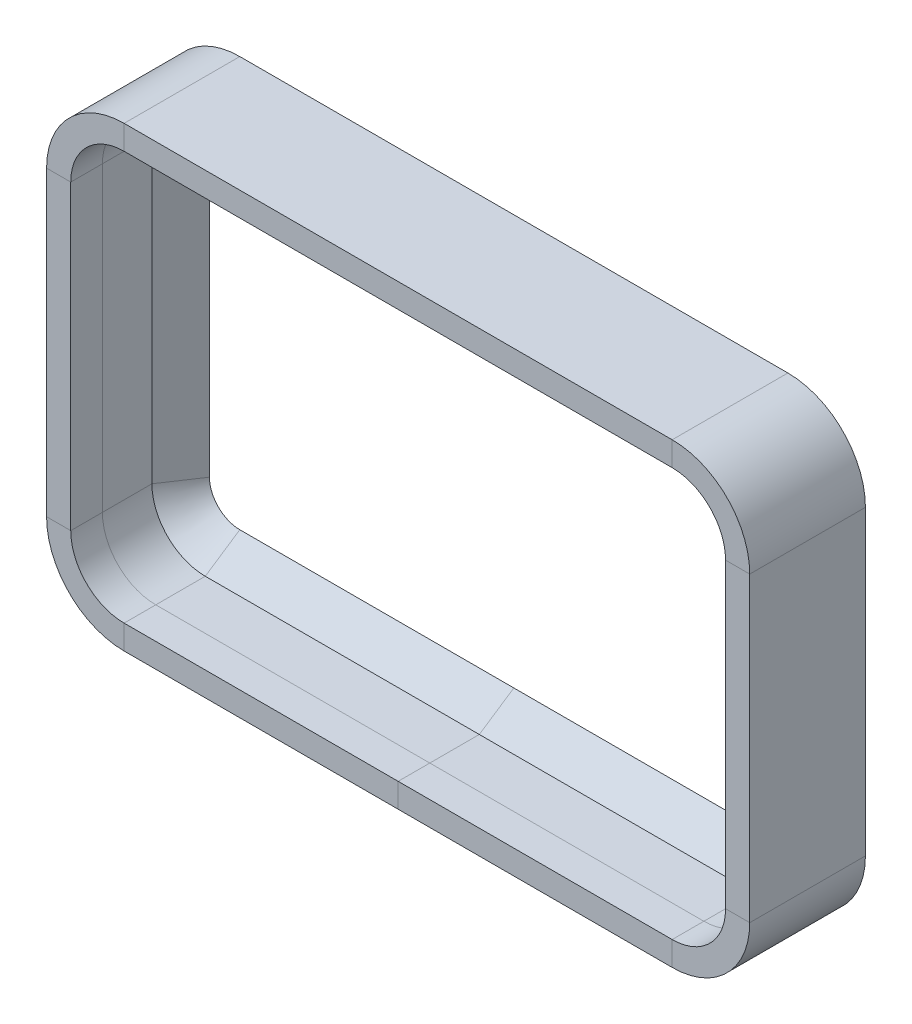
SolidWorks part; units mm, degrees
ref_plane "Plan de face" through (0, 0, 0) normal (0, 0, 1) x (1, 0, 0)
ref_plane "Plan de dessus" through (0, 0, 0) normal (0, 1, 0) x (1, 0, 0)
ref_plane "Plan de droite" through (0, 0, 0) normal (1, 0, 0) x (0, 0, -1)
sketch "Esquisse1" plane through (0, 0, 0) normal (0, 0, 1) x (1, 0, 0)
  line L1 (-39.6342, 31.8306) -> (39.6342, 31.8306)
  line L2 (-49.6342, 21.8306) -> (-49.6342, -21.8306)
  line L3 (-39.6342, -31.8306) -> (39.6342, -31.8306)
  line L4 (49.6342, 21.8306) -> (49.6342, -21.8306)
  line L5 (-49.6342, 31.8306) -> (49.6342, -31.8306) construction
  line L6 (-49.6342, -31.8306) -> (49.6342, 31.8306) construction
  arc A0 (-49.6342, -21.8306) -> (-39.6342, -31.8306) centre (-39.6342, -21.8306) ccw
  arc A1 (39.6342, -31.8306) -> (49.6342, -21.8306) centre (39.6342, -21.8306) ccw
  arc A2 (39.6342, 31.8306) -> (49.6342, 21.8306) centre (39.6342, 21.8306) cw
  arc A3 (-39.6342, 31.8306) -> (-49.6342, 21.8306) centre (-39.6342, 21.8306) ccw
  point P0 (0, 0)
  dimension "D1" = 10
sketch "Esquisse2" plane through (0, 0, 0) normal (1, 0, 0) x (0, 0, -1)
  line L0 (-2.0811, -29.5514) -> (5.0778, -29.5514)
  line L1 (5.0778, -29.5514) -> (10.0724, -26.2216)
  line L2 (10.0724, -26.2216) -> (10.0724, -33.0476)
  line L3 (10.0724, -33.0476) -> (-6.6595, -33.0476)
  line L4 (-6.6595, -33.0476) -> (-6.6595, -29.5514)
  line L5 (-6.6595, -29.5514) -> (-2.0811, -29.5514)
sweep "Balayage1" add profiles "Esquisse2" path "Esquisse1"
